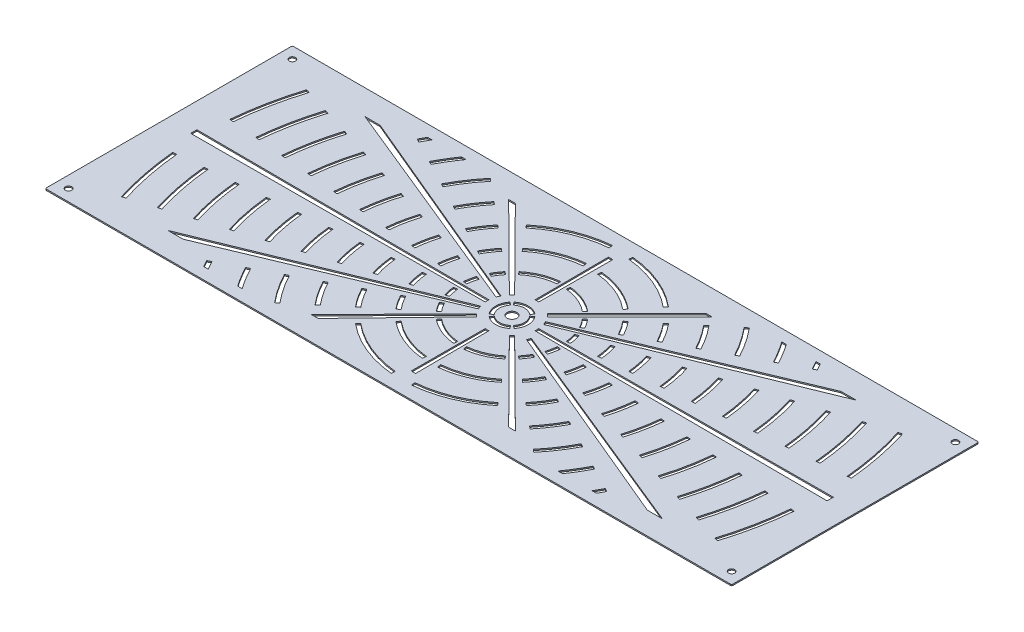
SolidWorks part; units mm, degrees
material "ASTM A36 Acier"
ref_plane "Front Plane" through (0, 0, 0) normal (0, 0, 1) x (1, 0, 0)
ref_plane "Top Plane" through (0, 0, 0) normal (0, 1, 0) x (1, 0, 0)
ref_plane "Right Plane" through (0, 0, 0) normal (1, 0, 0) x (0, 0, -1)
sketch "Sketch2" plane through (0, 0, 0) normal (0, 1, 0) x (1, 0, 0)
  line L1 (-275, -99) -> (275, -99)
  line L2 (-275, -99) -> (-275, 99)
  line L3 (-275, 99) -> (275, 99)
  line L4 (275, -99) -> (275, 99)
  line L5 (-275, -99) -> (275, 99) construction
  line L6 (-275, 99) -> (275, -99) construction
  point P0 (0, 0)
  dimension "D1" = 198
  dimension "D2" = 550
base flange "Base-Flange1" sketch "Sketch2" thickness 1 reverse thickness direction no parameters "D1"=1
sketch "Sketch7" plane through (0, 0, 0) normal (0, 1, 0) x (1, 0, 0)
  line L0 (-225, 89.6667) -> (-1.3167, 89.6667) construction
  line L1 (275, -99) -> (275, 99) construction
  line L2 (-275, -99) -> (275, -99) construction
  line L4 (275, 99) -> (-275, 99) construction
  line L5 (265.6667, 89.6667) -> (265.6667, -89.6667) construction
  line L6 (265.6667, -89.6667) -> (-265.6667, -89.6667) construction
  line L7 (-265.6667, -89.6667) -> (-265.6667, 89.6667) construction
  circle A0 centre (-265.6667, 89.6667) radius 2.5
  circle A1 centre (-265.6667, -89.6667) radius 2.5
  circle A2 centre (265.6667, -89.6667) radius 2.5
  circle A3 centre (265.6667, 89.6667) radius 2.5
  dimension "D3" = 5
  dimension "D1" = 9.3333
  dimension "D2" = 9.3333
  dimension "D4" = 9.3333
  dimension "D5" = 531.3333
extrude "Cut-Extrude1" cut sketch "Sketch7" against normal through all normal cut yes
pattern_linear "Répétition linéaire1" [suppressed] count 78 spacing 7 count 28 spacing 7
sketch "Esquisse21" plane through (0, 0, 0) normal (0, 1, 0) x (1, 0, 0)
  line L0 (0, 0) -> (0, 50000) construction
  line L1 (0, 0) -> (50000, 0) construction
  line L2 (0, 0) -> (46193.9766, 19134.1716) construction
  line L3 (0.0845, -0.0845) -> (-35355.2545, 35355.2545) construction
  line L4 (0, 0) -> (35355.3391, 35355.3391) construction
  line L5 (0, 0) -> (-19134.1716, 46193.9766) construction
  line L6 (0, 0) -> (19134.1716, 46193.9766) construction
  line L7 (0, 0) -> (-46193.9766, 19134.1716) construction
  line L8 (0, 0) -> (49039.264, 9754.5161) construction
  line L9 (0, 0) -> (-49039.264, 9754.5161) construction
  line L10 (20, -1.5) -> (20, 1.5)
  line L11 (20, 1.5) -> (255, 2.5254)
  line L12 (255, 2.5254) -> (255, -2.5254)
  line L13 (255, -2.5254) -> (20, -1.5)
  line L14 (275, -99) -> (275, 99) construction
  line L15 (8.3562, 9.9586) -> (6.4279, 7.6604)
  line L16 (6.4279, 7.6604) -> (0, 0) construction
  line L17 (9.9586, 8.3562) -> (7.6604, 6.4279)
  line L18 (7.6604, 6.4279) -> (0, 0)
  line L19 (8.3562, -9.9586) -> (6.4279, -7.6604)
  line L20 (9.9586, -8.3562) -> (7.6604, -6.4279)
  line L21 (-9.9586, -8.3562) -> (-7.6604, -6.4279)
  line L22 (-8.3562, -9.9586) -> (-6.4279, -7.6604)
  line L23 (-8.3562, 9.9586) -> (-6.4279, 7.6604)
  line L24 (-9.9586, 8.3562) -> (-7.6604, 6.4279)
  line L25 (-1.5, 20) -> (1.5, 20)
  line L26 (1.5, 20) -> (1.7574, 79)
  line L27 (1.7574, 79) -> (-1.7574, 79)
  line L28 (-1.7574, 79) -> (-1.5, 20)
  line L29 (275, 99) -> (-275, 99) construction
  line L31 (-255, -2.5257) -> (-255, 2.5251)
  line L32 (-255, 2.5251) -> (-20, 1.5)
  line L33 (-20, 1.5) -> (-20, -1.5)
  line L34 (-1.5, -20) -> (-1.7574, -79)
  line L35 (1.7575, -79) -> (1.5, -20)
  line L36 (1.5, -20) -> (-1.5, -20)
  line L37 (-1.7574, -79) -> (1.7575, -79)
  line L38 (-15.2028, 13.0815) -> (-13.0815, 15.2028)
  line L39 (-13.0815, 15.2028) -> (-76.3129, 79)
  line L40 (-76.3129, 79) -> (-81.6871, 79)
  line L41 (-81.6871, 79) -> (-15.2028, 13.0815)
  line L42 (13.0815, -15.2028) -> (76.3129, -79)
  line L43 (81.6871, -79) -> (15.2028, -13.0815)
  line L44 (15.2028, -13.0815) -> (13.0815, -15.2028)
  line L45 (76.3129, -79) -> (81.6871, -79)
  line L46 (14.1421, -14.1421) -> (79, -79) construction
  line L47 (13.0815, 15.2028) -> (15.2028, 13.0815)
  line L48 (15.2028, 13.0815) -> (81.6871, 79)
  line L49 (81.6871, 79) -> (76.3129, 79)
  line L50 (76.3129, 79) -> (13.0815, 15.2028)
  line L51 (-75.4279, -79.8395) -> (-13.0686, -15.1895)
  line L52 (-15.2185, -13.0971) -> (-80.8015, -79.9125)
  line L53 (-80.8015, -79.9125) -> (-75.4279, -79.8395)
  line L54 (-13.0686, -15.1895) -> (-15.2185, -13.0971)
  line L55 (-20, -1.5) -> (-255, -2.5257) [skipped]
  line L56 (-255, -2.5257) -> (-20, -1.5)
  circle A0 centre (0, 0) radius 4
  arc A1 (6.4279, 7.6604) -> (-6.4279, 7.6604) centre (0, 0) ccw
  arc A2 (8.3562, 9.9586) -> (-8.3562, 9.9586) centre (0, 0) ccw
  arc A3 (-9.9586, 8.3562) -> (-9.9586, -8.3562) centre (0, 0) ccw
  arc A4 (-7.6604, 6.4279) -> (-7.6604, -6.4279) centre (0, 0) ccw
  arc A5 (-6.4279, -7.6604) -> (6.4279, -7.6604) centre (0, 0) ccw
  arc A6 (-8.3562, -9.9586) -> (8.3562, -9.9586) centre (0, 0) ccw
  arc A7 (9.9586, -8.3562) -> (9.9586, 8.3562) centre (0, 0) ccw
  arc A8 (7.6604, -6.4279) -> (7.6604, 6.4279) centre (0, 0) ccw
  point P24 (20, 0)
  point P28 (255, 0)
  point P38 (0, 79)
  point P52 (0, 0)
  point P54 (0, 20)
  point P57 (0.0001, -79)
  point P67 (0, 0)
  point P68 (-79, 79)
  point P72 (0, -20)
  point P73 (-14.1421, 14.1421)
  point P80 (0, 0)
  point P83 (14.1421, 14.1421)
  point P84 (14.1421, -14.1421)
  point P88 (79, 79)
  point P93 (-0.0968, 0.0955)
  dimension "D13" = 8
  dimension "D14" = 10
  dimension "D16" = 20
  dimension "D17" = 3
  dimension "D1" = 22.5
  dimension "D2" = 22.5
  dimension "D3" = 22.5
  dimension "D4" = 22.5
  dimension "D5" = 22.5
  dimension "D6" = 22.5
  dimension "D7" = 11.25
  dimension "D8" = 11.25
  dimension "D9" = 3
  dimension "D10" = 20
  dimension "D11" = 0.5
  dimension "D12" = 20
  dimension "D15" = 5
  dimension "D19" = 0.5
  dimension "D20" = 3
  dimension "D21" = 20
  dimension "D22" = 20
  dimension "D24" = 20
  dimension "D25" = 0.5
  dimension "D26" = 20
  dimension "D27" = 3
  dimension "D29" = 20
  dimension "D30" = 3
  dimension "D31" = 0.5
  dimension "D33" = 20
  dimension "D18" = 4
  dimension "D23" = 2
  dimension "D28" = 2
  dimension "D32" = 2
extrude "Enlèv. mat.-Extru.2" cut sketch "Esquisse21" against normal blind 10
sketch "Esquisse36" plane through (0, 0, 0) normal (0, 1, 0) x (1, 0, 0)
  line L0 (0, 0) -> (50000, 0) construction
  line L1 (0, 0) -> (-46193.9766, 19134.1716) construction
  line L2 (0, 0) -> (46193.9766, 19134.1716) construction
  line L3 (17.9036, 9.0395) -> (19.0516, 6.2678)
  line L4 (19.0516, 6.2678) -> (196.7664, 79)
  line L5 (196.7664, 79) -> (184.6793, 79)
  line L6 (184.6793, 79) -> (17.9036, 9.0395)
  line L7 (81.6871, 79) -> (76.3129, 79) construction
  line L8 (-19.0516, -6.2678) -> (-196.7664, -79)
  line L9 (-184.6793, -79) -> (-17.9036, -9.0395)
  line L10 (-196.7664, -79) -> (-184.6793, -79)
  line L11 (-17.9036, -9.0395) -> (-19.0516, -6.2678)
  line L12 (-19.0516, 6.2678) -> (-17.9036, 9.0395)
  line L13 (-17.9036, 9.0395) -> (-184.6793, 79)
  line L14 (-184.6793, 79) -> (-196.7664, 79)
  line L15 (-196.7664, 79) -> (-19.0516, 6.2678)
  line L18 (-76.3129, 79) -> (-81.6871, 79) construction
  line L19 (22.66, -11.0691) -> (189.4482, -81)
  line L20 (189.4482, -81) -> (201.5352, -80.9979)
  line L21 (201.5352, -80.9979) -> (23.8075, -8.2973)
  line L22 (23.8075, -8.2973) -> (22.66, -11.0691)
  arc A0 (9.9586, -8.3562) -> (9.9586, 8.3562) centre (0, 0) ccw construction
  arc A1 (-9.9586, 8.3562) -> (-9.9586, -8.3562) centre (0, 0) ccw construction
  point P10 (18.4776, 7.6537)
  point P14 (190.7229, 79)
  point P25 (0, 0)
  point P30 (-18.4776, 7.6537)
  point P34 (-190.7229, 79)
  point P41 (2.3773, -1.0166)
  dimension "D1" = 22.5
  dimension "D2" = 22.5
  dimension "D3" = 3
  dimension "D4" = 0.5
  dimension "D5" = 20
  dimension "D7" = 20
  dimension "D8" = 20
  dimension "D9" = 0.5
  dimension "D10" = 3
  dimension "D6" = 2
  dimension "D11" = 2
extrude "Enlèv. mat.-Extru.3" cut sketch "Esquisse36" against normal through all contours L9 L11 L8 L10 | L14 L15 L12 L13 | L4 L5 L6 L3 | L21 L22 L19 L20 normal cut yes
sketch "Esquisse37" plane through (0, 0, 0) normal (0, 1, 0) x (1, 0, 0)
  line L0 (3.6652, 39.8881) -> (3.9397, 42.8755)
  line L1 (27.5288, 33.1059) -> (25.6107, 30.7992)
  line L2 (1.5, 20) -> (1.7574, 79) construction
  line L3 (76.3129, 79) -> (13.0815, 15.2028) construction
  line L4 (5.7697, 62.7916) -> (6.0442, 65.7791)
  line L5 (42.2343, 50.7906) -> (40.3162, 48.4839)
  line L6 (3.9397, 42.8755) -> (5.7697, 62.7916) construction
  line L7 (27.5288, 33.1059) -> (40.3162, 48.4839) construction
  line L8 (30.7945, 25.6163) -> (33.1009, 27.5348)
  line L9 (38.1016, 20.0526) -> (35.4468, 18.6554)
  line L10 (15.2028, 13.0815) -> (81.6871, 79) construction
  line L11 (184.6793, 79) -> (17.9036, 9.0395) construction
  line L12 (33.1009, 27.5348) -> (48.4766, 40.325)
  line L13 (48.4766, 40.325) -> (50.7829, 42.2435)
  line L14 (58.4549, 30.7644) -> (55.8001, 29.3672)
  line L15 (55.8001, 29.3672) -> (38.1016, 20.0526) construction
  line L16 (50.7829, 42.2435) -> (66.1586, 55.0337) construction
  line L17 (66.1586, 55.0337) -> (68.465, 56.9522)
  line L18 (78.8082, 41.4761) -> (76.1534, 40.079)
  line L19 (76.1534, 40.079) -> (58.4549, 30.7644) construction
  line L20 (68.465, 56.9522) -> (83.8406, 69.7423) construction
  line L21 (83.8406, 69.7423) -> (86.147, 71.6609)
  line L22 (99.1615, 52.1879) -> (96.5067, 50.7907)
  line L23 (96.5067, 50.7907) -> (78.8082, 41.4761) construction
  line L24 (38.2529, 11.8833) -> (41.1178, 12.7733)
  line L25 (42.8755, 3.9397) -> (39.8881, 3.6652)
  line L26 (0, 0) -> (39.8881, 3.6652) construction
  line L27 (0, 0) -> (38.2529, 11.8833) construction
  line L28 (19.0516, 6.2678) -> (196.7664, 79) construction
  line L29 (20, 1.5) -> (255, 2.5254) construction
  line L30 (60.2175, 18.7066) -> (63.0824, 19.5966)
  line L31 (65.7791, 6.0442) -> (62.7916, 5.7697)
  line L32 (82.182, 25.53) -> (85.047, 26.42)
  line L33 (88.6826, 8.1488) -> (85.6952, 7.8743)
  line L34 (104.1466, 32.3533) -> (107.0115, 33.2433)
  line L35 (111.5861, 10.2533) -> (108.5987, 9.9788)
  line L36 (126.1112, 39.1766) -> (128.9761, 40.0666)
  line L37 (134.4896, 12.3579) -> (131.5022, 12.0834)
  line L38 (148.0757, 46) -> (150.9407, 46.89)
  line L39 (157.3931, 14.4624) -> (154.4057, 14.1879)
  line L40 (170.0403, 52.8233) -> (172.9052, 53.7133)
  line L41 (180.2966, 16.5669) -> (177.3092, 16.2924)
  line L42 (192.0049, 59.6466) -> (194.8698, 60.5366)
  line L43 (203.2001, 18.6715) -> (200.2127, 18.397)
  line L44 (6.0442, 65.7791) -> (7.8743, 85.6952) construction
  line L45 (7.8743, 85.6952) -> (8.1488, 88.6826)
  line L46 (56.9398, 68.4753) -> (55.0217, 66.1686)
  line L47 (42.2343, 50.7906) -> (55.0217, 66.1686) construction
  line L48 (86.147, 71.6609) -> (101.5227, 84.451) construction
  line L49 (101.5227, 84.451) -> (103.829, 86.3696)
  line L50 (119.5148, 62.8997) -> (116.86, 61.5025)
  line L51 (116.86, 61.5025) -> (99.1615, 52.1879) construction
  line L52 (103.829, 86.3696) -> (119.2047, 99.1597) construction
  line L54 (139.8681, 73.6115) -> (137.2134, 72.2143)
  line L55 (137.2134, 72.2143) -> (119.5148, 62.8997) construction
  line L56 (126.5002, 89.6667) -> (130.1601, 89.6667)
  line L57 (265.6667, -89.6667) -> (-265.6667, -89.6667) construction
  line L58 (265.6667, -89.6667) -> (265.6667, 89.6667) construction
  line L59 (265.6667, 89.6667) -> (-265.6667, 89.6667) construction
  line L60 (-265.6667, -89.6667) -> (-265.6667, 89.6667) construction
  line L61 (265.6667, -89.6667) -> (-265.6667, 89.6667) construction
  line L62 (265.6667, 89.6667) -> (-265.6667, -89.6667) construction
  line L63 (139.8681, 73.6115) -> (157.5667, 82.9261)
  line L64 (157.5667, 82.9261) -> (160.2215, 84.3233)
  line L65 (157.2934, 89.6667) -> (153.8307, 89.6667)
  line L66 (153.8307, 89.6667) -> (157.5667, 82.9261)
  line L67 (213.9694, 66.4699) -> (216.8344, 67.3599)
  line L68 (226.1037, 20.776) -> (223.1162, 20.5015)
  line L69 (235.934, 73.2933) -> (238.7989, 74.1833)
  line L70 (249.0072, 22.8805) -> (246.0198, 22.606)
  circle A0 centre (0, 0) radius 20.0562 construction
  circle A1 centre (0, 0) radius 40.0562 construction
  circle A2 centre (0, 0) radius 43.0562 construction
  circle A3 centre (0, 0) radius 63.0562 construction
  circle A4 centre (0, 0) radius 66.0562 construction
  circle A5 centre (0, 0) radius 86.0562 construction
  circle A6 centre (0, 0) radius 89.0562 construction
  circle A7 centre (0, 0) radius 109.0562 construction
  circle A8 centre (0, 0) radius 112.0562 construction
  circle A9 centre (0, 0) radius 132.0562 construction
  circle A10 centre (0, 0) radius 135.0562 construction
  arc A11 (119.2047, 99.1597) -> (126.5002, 89.6667) centre (0, 0) ccw construction
  arc A12 (122.7749, 99.5393) -> (130.1601, 89.6667) centre (0, 0) ccw construction
  circle A13 centre (0, 0) radius 178.0562 construction
  circle A14 centre (0, 0) radius 181.0562 construction
  circle A15 centre (0, 0) radius 201.0562 construction
  circle A16 centre (0, 0) radius 204.0562 construction
  circle A17 centre (0, 0) radius 224.0562 construction
  circle A18 centre (0, 0) radius 227.0562 construction
  circle A19 centre (0, 0) radius 250.0562 construction
  circle A20 centre (0, 0) radius 247.0562 construction
  arc A21 (3.9397, 42.8755) -> (27.5288, 33.1059) centre (0, 0) cw
  arc A22 (25.6107, 30.7992) -> (3.6652, 39.8881) centre (0, 0) ccw
  arc A23 (6.0442, 65.7791) -> (42.2343, 50.7906) centre (0, 0) cw
  arc A24 (40.3162, 48.4839) -> (5.7697, 62.7916) centre (0, 0) ccw
  arc A25 (33.1009, 27.5348) -> (38.1016, 20.0526) centre (0, 0) cw
  arc A26 (35.4468, 18.6554) -> (30.7945, 25.6163) centre (0, 0) ccw
  arc A27 (50.7829, 42.2435) -> (58.4549, 30.7644) centre (0, 0) cw
  arc A28 (55.8001, 29.3672) -> (48.4766, 40.325) centre (0, 0) ccw
  arc A29 (68.465, 56.9522) -> (78.8082, 41.4761) centre (0, 0) cw
  arc A30 (76.1534, 40.079) -> (66.1586, 55.0337) centre (0, 0) ccw
  arc A31 (86.147, 71.6609) -> (99.1615, 52.1879) centre (0, 0) cw
  arc A32 (96.5067, 50.7907) -> (83.8406, 69.7423) centre (0, 0) ccw
  arc A33 (41.1178, 12.7733) -> (42.8755, 3.9397) centre (0, 0) cw
  arc A34 (39.8881, 3.6652) -> (38.2529, 11.8833) centre (0, 0) ccw
  arc A35 (63.0824, 19.5966) -> (65.7791, 6.0442) centre (0, 0) cw
  arc A36 (62.7916, 5.7697) -> (60.2175, 18.7066) centre (0, 0) ccw
  arc A37 (85.047, 26.42) -> (88.6826, 8.1488) centre (0, 0) cw
  arc A38 (85.6952, 7.8743) -> (82.182, 25.53) centre (0, 0) ccw
  arc A39 (107.0115, 33.2433) -> (111.5861, 10.2533) centre (0, 0) cw
  arc A40 (108.5987, 9.9788) -> (104.1466, 32.3533) centre (0, 0) ccw
  arc A41 (128.9761, 40.0666) -> (134.4896, 12.3579) centre (0, 0) cw
  arc A42 (131.5022, 12.0834) -> (126.1112, 39.1766) centre (0, 0) ccw
  arc A43 (150.9407, 46.89) -> (157.3931, 14.4624) centre (0, 0) cw
  arc A44 (154.4057, 14.1879) -> (148.0757, 46) centre (0, 0) ccw
  arc A45 (172.9052, 53.7133) -> (180.2966, 16.5669) centre (0, 0) cw
  arc A46 (177.3092, 16.2924) -> (170.0403, 52.8233) centre (0, 0) ccw
  arc A47 (194.8698, 60.5366) -> (203.2001, 18.6715) centre (0, 0) cw
  arc A48 (200.2127, 18.397) -> (192.0049, 59.6466) centre (0, 0) ccw
  arc A49 (8.1488, 88.6826) -> (56.9398, 68.4753) centre (0, 0) cw
  arc A50 (55.0217, 66.1686) -> (7.8743, 85.6952) centre (0, 0) ccw
  arc A51 (103.829, 86.3696) -> (119.5148, 62.8997) centre (0, 0) cw
  arc A52 (101.5227, 84.451) -> (116.86, 61.5025) centre (0, 0) cw
  arc A53 (130.1601, 89.6667) -> (139.8681, 73.6115) centre (0, 0) cw
  arc A54 (137.2134, 72.2143) -> (126.5002, 89.6667) centre (0, 0) ccw
  arc A55 (160.2215, 84.3233) -> (157.2934, 89.6667) centre (0, 0) ccw
  arc A56 (216.8344, 67.3599) -> (226.1037, 20.776) centre (0, 0) cw
  arc A57 (223.1162, 20.5015) -> (213.9694, 66.4699) centre (0, 0) ccw
  arc A58 (238.7989, 74.1833) -> (249.0072, 22.8805) centre (0, 0) cw
  arc A59 (246.0198, 22.606) -> (235.934, 73.2933) centre (0, 0) ccw
  dimension "D1" = 20
  dimension "D2" = 3
  dimension "D3" = 20
  dimension "D4" = 3
  dimension "D5" = 20
  dimension "D6" = 3
  dimension "D7" = 20
  dimension "D8" = 3
  dimension "D9" = 20
  dimension "D10" = 3
  dimension "D11" = 20
  dimension "D12" = 3
  dimension "D13" = 20
  dimension "D14" = 3
  dimension "D15" = 20
  dimension "D16" = 3
  dimension "D17" = 20
  dimension "D18" = 3
  dimension "D19" = 20
  dimension "D20" = 3
  dimension "D21" = 5
  dimension "D23" = 5
  dimension "D25" = 5
  dimension "D22" = 5
  dimension "D24" = 5
  dimension "D26" = 5
extrude "Enlèv. mat.-Extru.4" cut sketch "Esquisse37" against normal through all
pattern_circular "Répétition circulaire1" count 2 every 180 about axis through (0, 0, 0) along (0, 1, 0) of "Enlèv. mat.-Extru.4"
mirror "Symétrie1" about plane through (0, 0, 0) normal (0, 0, 1) of "Répétition circulaire1", "Enlèv. mat.-Extru.4"
fillet "Congé1" radius 1 4 edges at (-275, -0.5, -99) (-275, -0.5, 99) (275, -0.5, 99) (275, -0.5, -99)
sketch "Esquisse38" [suppressed] plane through (0, 0, 0) normal (0, 1, 0) x (1, 0, 0)
  line L0 (-274, -100) -> (274, -100) construction
  line L1 (0, -100) -> (275, -100)
  line L3 (0, 100) -> (275, 100)
  line L4 (275, -100) -> (275, 100)
  line L7 (275, -99) -> (275, 99) construction
  line L8 (274, 100) -> (-274, 100) construction
  arc A1 (0, 100) -> (0, 0) centre (109.0871, 50) ccw
  arc A2 (0, 0) -> (0, -100) centre (-109.0871, -50) cw
  dimension "D1" = 120
extrude "Enlèv. mat.-Extru.5" [suppressed] cut sketch "Esquisse38" against normal through all
sketch "Bend-Lines1" [suppressed] plane through (0, 0, 0) normal (0, 1, 0) x (1, 0, 0)
sketch "Bounding-Box1" [suppressed] plane through (0, 0, 0) normal (0, 1, 0) x (1, 0, 0)
sheet metal parameters "Sheet-Metal1" thickness 1 parameters "D1"=1
flat pattern "Flat-Pattern1" [suppressed]
sketch "Bend-Lines2" plane through (0, 0, 0) normal (0, 1, 0) x (1, 0, 0)
sketch3d "Bounding-Box2" [suppressed]
  line L0 (-250, 50, 0) -> (250, 50, 0) construction
  line L1 (-250, -50, 0) -> (250, -50, 0) construction
  line L2 (-250, 50, 0) -> (-250, -50, 0) construction
  line L3 (250, 50, 0) -> (250, -50, 0) construction
sheet metal parameters "Sheet-Metal2" thickness 1 parameters "D1"=1
flat pattern "Flat-Pattern1"
sketch "Bend-Lines2" plane through (0, 0, 0) normal (0, 1, 0) x (1, 0, 0)
sketch3d "Bounding-Box2" [suppressed]
  line L0 (275, 101, 0) -> (-275, 101, 0) construction
  line L1 (275, -101, 0) -> (-275, -101, 0) construction
  line L2 (275, 101, 0) -> (275, -101, 0) construction
  line L3 (-275, 101, 0) -> (-275, -101, 0) construction
sheet metal parameters "Tôlerie3" thickness 1 parameters "D1"=1
flat pattern "Flat-Pattern1"
sketch "Bend-Lines2" plane through (0, 0, 0) normal (0, 1, 0) x (1, 0, 0)
sketch3d "Bounding-Box2" [suppressed]
  line L0 (275, 100, 0) -> (-275, 100, 0) construction
  line L1 (275, -100, 0) -> (-275, -100, 0) construction
  line L2 (275, 100, 0) -> (275, -100, 0) construction
  line L3 (-275, 100, 0) -> (-275, -100, 0) construction
sheet metal parameters "Tôlerie13" thickness 1 parameters "D1"=1
flat pattern "Etat déplié13"
sketch "Lignes de pliage10" plane through (0, 0, 0) normal (0, 1, 0) x (1, 0, 0)
sketch3d "Cube de visualisation10" [suppressed]
  line L0 (275, 101, 0) -> (-275, 101, 0) construction
  line L1 (275, -101, 0) -> (-275, -101, 0) construction
  line L2 (275, 101, 0) -> (275, -101, 0) construction
  line L3 (-275, 101, 0) -> (-275, -101, 0) construction
sheet metal parameters "Tôlerie14" thickness 1 parameters "D1"=1
flat pattern "Etat déplié14"
sketch "Lignes de pliage11" plane through (0, 0, 0) normal (0, 1, 0) x (1, 0, 0)
sketch3d "Cube de visualisation11" [suppressed]
  line L0 (84.9232, -36.5963, 0) -> (38.9548, 90.8726, 0) construction
  line L1 (-42.465, -82.5357, 0) -> (-88.4335, 44.9332, 0) construction
  line L2 (84.9232, -36.5963, 0) -> (-42.465, -82.5357, 0) construction
  line L3 (38.9548, 90.8726, 0) -> (-88.4335, 44.9332, 0) construction
sheet metal parameters "Tôlerie15" thickness 1 parameters "D1"=1
flat pattern "Etat déplié15"
sketch "Lignes de pliage12" plane through (0, 0, 0) normal (0, 1, 0) x (1, 0, 0)
sketch3d "Cube de visualisation12" [suppressed]
  line L0 (53.1141, 35.9815, 0) -> (-40.1929, 42.9646, 0) construction
  line L1 (49.7678, -8.7313, 0) -> (-43.5392, -1.7482, 0) construction
  line L2 (53.1141, 35.9815, 0) -> (49.7678, -8.7313, 0) construction
  line L3 (-40.1929, 42.9646, 0) -> (-43.5392, -1.7482, 0) construction
sheet metal parameters "Tôlerie16" thickness 1 parameters "D1"=1
flat pattern "Etat déplié16"
sketch "Lignes de pliage13" plane through (0, 0, 0) normal (0, 1, 0) x (1, 0, 0)
sketch3d "Cube de visualisation13" [suppressed]
  line L0 (46.6794, -8.3193, 0) -> (-25.4058, -0.6713, 0) construction
  line L1 (45.2806, -21.5033, 0) -> (-26.8046, -13.8553, 0) construction
  line L2 (46.6794, -8.3193, 0) -> (45.2806, -21.5033, 0) construction
  line L3 (-25.4058, -0.6713, 0) -> (-26.8046, -13.8553, 0) construction
sheet metal parameters "Tôlerie17" thickness 1 parameters "D1"=1
flat pattern "Etat déplié17"
sketch "Lignes de pliage14" plane through (0, 0, 0) normal (0, 1, 0) x (1, 0, 0)
sketch3d "Cube de visualisation14" [suppressed]
  line L0 (-6.0842, 1.2958, 0) -> (-7.2286, 29.2154, 0) construction
  line L1 (-14.229, 0.9619, 0) -> (-15.3734, 28.8816, 0) construction
  line L2 (-6.0842, 1.2958, 0) -> (-14.229, 0.9619, 0) construction
  line L3 (-7.2286, 29.2154, 0) -> (-15.3734, 28.8816, 0) construction
sheet metal parameters "Tôlerie18" thickness 1 parameters "D1"=1
flat pattern "Etat déplié18"
sketch "Lignes de pliage15" plane through (0, 0, 0) normal (0, 1, 0) x (1, 0, 0)
sketch3d "Cube de visualisation15" [suppressed]
  line L0 (45.1508, -7.3989, 0) -> (49.285, 1.4003, 0) construction
  line L1 (49.2315, -9.3162, 0) -> (53.3657, -0.517, 0) construction
  line L2 (45.1508, -7.3989, 0) -> (49.2315, -9.3162, 0) construction
  line L3 (49.285, 1.4003, 0) -> (53.3657, -0.517, 0) construction
sheet metal parameters "Tôlerie19" thickness 1 parameters "D1"=1
flat pattern "Etat déplié19"
sketch "Lignes de pliage16" plane through (0, 0, 0) normal (0, 1, 0) x (1, 0, 0)
sketch3d "Cube de visualisation16" [suppressed]
  line L0 (-37.6379, 47.9062, 0) -> (-40.3472, 50.5756, 0) construction
  line L1 (-40.0979, 45.4094, 0) -> (-42.8072, 48.0787, 0) construction
  line L2 (-37.6379, 47.9062, 0) -> (-40.0979, 45.4094, 0) construction
  line L3 (-40.3472, 50.5756, 0) -> (-42.8072, 48.0787, 0) construction
sheet metal parameters "Tôlerie20" thickness 1 parameters "D1"=1
flat pattern "Flat-Pattern1"
sketch "Bend-Lines2" plane through (0, 0, 0) normal (0, 1, 0) x (1, 0, 0)
sketch3d "Bounding-Box2" [suppressed]
  line L0 (275, 101, 0) -> (-275, 101, 0) construction
  line L1 (275, -101, 0) -> (-275, -101, 0) construction
  line L2 (275, 101, 0) -> (275, -101, 0) construction
  line L3 (-275, 101, 0) -> (-275, -101, 0) construction
sheet metal parameters "Tôlerie21" thickness 1 parameters "D1"=1
flat pattern "Flat-Pattern1"
sketch "Bend-Lines2" plane through (0, 0, 0) normal (0, 1, 0) x (1, 0, 0)
sketch3d "Bounding-Box2" [suppressed]
  line L0 (275, 101, 0) -> (-275, 101, 0) construction
  line L1 (275, -101, 0) -> (-275, -101, 0) construction
  line L2 (275, 101, 0) -> (275, -101, 0) construction
  line L3 (-275, 101, 0) -> (-275, -101, 0) construction
sheet metal parameters "Tôlerie22" thickness 1 parameters "D1"=1
flat pattern "Flat-Pattern1"
sketch "Bend-Lines2" plane through (0, 0, 0) normal (0, 1, 0) x (1, 0, 0)
sketch3d "Bounding-Box2" [suppressed]
  line L0 (275, 101, 0) -> (-275, 101, 0) construction
  line L1 (275, -101, 0) -> (-275, -101, 0) construction
  line L2 (275, 101, 0) -> (275, -101, 0) construction
  line L3 (-275, 101, 0) -> (-275, -101, 0) construction
sheet metal parameters "Tôlerie23" thickness 1 parameters "D1"=1
flat pattern "Flat-Pattern1"
sketch "Bend-Lines2" plane through (0, 0, 0) normal (0, 1, 0) x (1, 0, 0)
sketch3d "Bounding-Box2" [suppressed]
  line L0 (275, 101, 0) -> (-275, 101, 0) construction
  line L1 (275, -101, 0) -> (-275, -101, 0) construction
  line L2 (275, 101, 0) -> (275, -101, 0) construction
  line L3 (-275, 101, 0) -> (-275, -101, 0) construction
sheet metal parameters "Tôlerie24" thickness 1 parameters "D1"=1
flat pattern "Flat-Pattern1"
sketch "Bend-Lines2" plane through (0, 0, 0) normal (0, 1, 0) x (1, 0, 0)
sketch3d "Bounding-Box2" [suppressed]
  line L0 (275, 99, 0) -> (-275, 99, 0) construction
  line L1 (275, -99, 0) -> (-275, -99, 0) construction
  line L2 (275, 99, 0) -> (275, -99, 0) construction
  line L3 (-275, 99, 0) -> (-275, -99, 0) construction
sheet metal parameters "Tôlerie25" [suppressed] thickness 1 parameters "D1"=1
flat pattern "Flat-Pattern1"
sketch "Bend-Lines2" plane through (0, 0, 0) normal (0, 1, 0) x (1, 0, 0)
sketch3d "Bounding-Box2" [suppressed]
  line L0 (0, 100, 0) -> (-275, 100, 0) construction
  line L1 (0, -100, 0) -> (-275, -100, 0) construction
  line L2 (0, 100, 0) -> (0, -100, 0) construction
  line L3 (-275, 100, 0) -> (-275, -100, 0) construction
